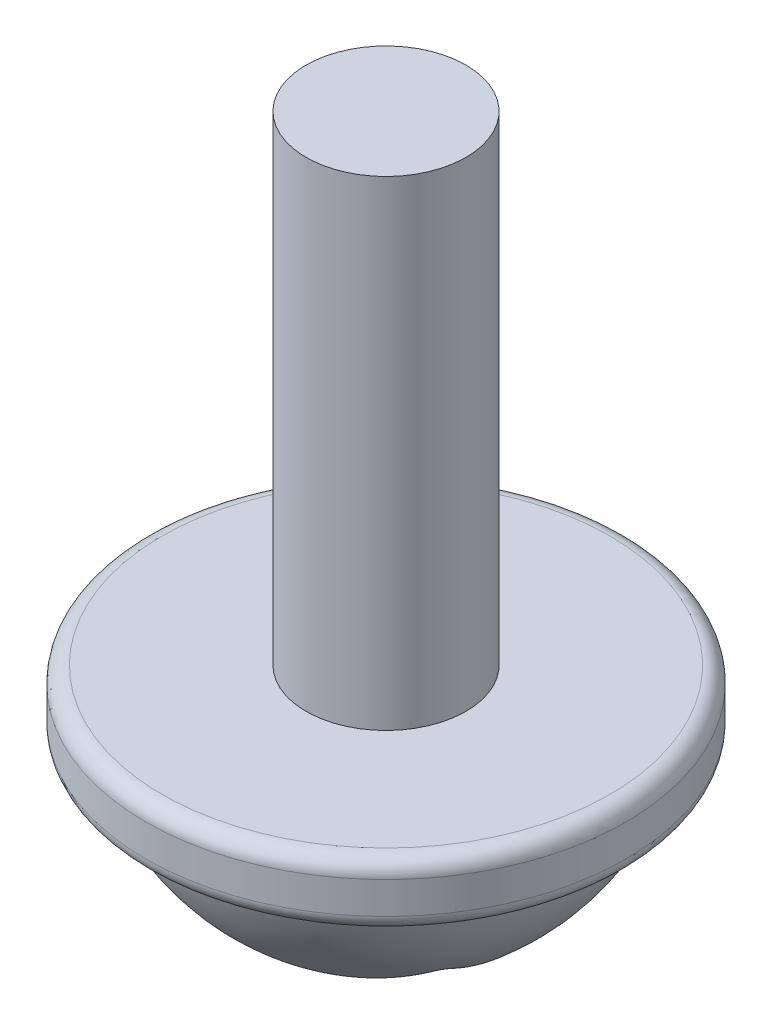
SolidWorks part; units mm, degrees
material "AISI 4140 Steel, quenched & tempered"
ref_plane "Front Plane" through (0, 0, 0) normal (1, 0, 0) x (0, 1, 0)
ref_plane "Top Plane" through (0, 0, 0) normal (0, 0, 1) x (0, 1, 0)
ref_plane "Right Plane" through (0, 0, 0) normal (0, 1, 0) x (-1, 0, 0)
sketch "Sketch1" plane through (0, 0, 0) normal (1, 0, 0) x (0, 1, 0)
  line L0 (-7.8413, 0) -> (12.7199, 0) construction
  line L1 (0, 5.1403) -> (0, -7.0185) construction
  line L2 (0, 2.5) -> (15, 2.5)
  line L3 (15, 2.5) -> (15, 0)
  line L4 (0, 2.5) -> (0, 7.5)
  line L5 (0, 7.5) -> (-2, 7.5)
  line L6 (-2, 7.5) -> (-2, 0)
  line L7 (-2, 0) -> (15, 0)
  line L8 (-7, 0) -> (-2, 0)
  arc A0 (-2, 6.5) -> (-7, 0) centre (-0.275, 0) ccw
  arc A1 (0, -5.3201) -> (0.3021, -5.2848) centre (-0.6029, 1.1519) ccw
  dimension "D5" = 6.5
  dimension "D1" = 5
  dimension "D2" = 15
  dimension "D3" = 2
  dimension "D4" = 15
  dimension "D6" = 5
revolve "Revolve1" add sketch "Sketch1" angle 360 about L0 region at (0, 5.0714, 1.9643) region at (0, -4.0816, 2.6293)
sketch "Sketch2" plane through (0, 0, 0) normal (0, 1, 0) x (-1, 0, 0)
  line L1 (0, 4.5) -> (-3.8971, 2.25)
  line L2 (-3.8971, 2.25) -> (-3.8971, -2.25)
  line L3 (-3.8971, -2.25) -> (0, -4.5)
  line L4 (0, -4.5) -> (3.8971, -2.25)
  line L5 (3.8971, -2.25) -> (3.8971, 2.25)
  line L6 (3.8971, 2.25) -> (0, 4.5)
  circle A0 centre (0, 0) radius 3.8971 construction
  dimension "D1" = 4.5
extrude "Cut-Extrude1" cut sketch "Sketch2" against normal blind 10 from offset 3 offset against normal yes
fillet "Fillet1" radius 0.5 2 edges at (0, 0, -7.5) (0, -2, -7.5)
fillet "Fillet2" radius 0.25 18 edges at (-1.9486, -3, 3.375) (1.9486, -3, 3.375) (3.8971, -3, 0) (1.9486, -3, -3.375) (-1.9486, -3, -3.375) (-3.8971, -3, 0) (0, -4.1363, 4.5) (3.8971, -4.1363, 2.25) (3.8971, -4.1363, -2.25) (0, -4.1363, -4.5) (-3.8971, -4.1363, -2.25) (-3.8971, -4.1363, 2.25) (1.9486, -5.7557, 3.375) (3.8971, -5.7557, 0) (1.9486, -5.7557, -3.375) (-1.9486, -5.7557, -3.375) (-1.9486, -5.7557, 3.375) (-3.8971, -5.7557, 0)
